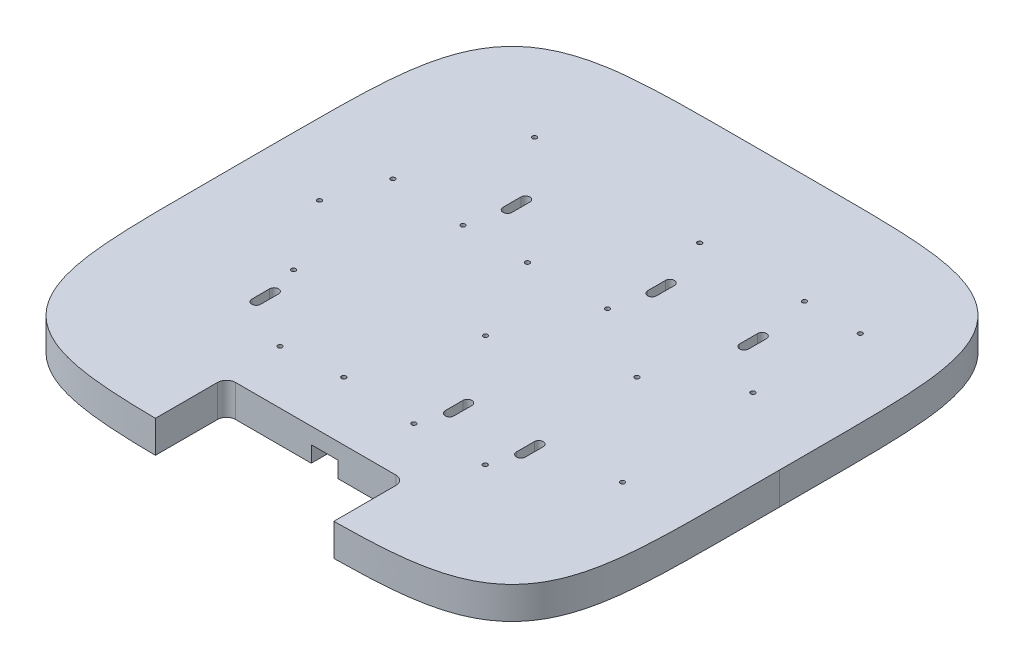
SolidWorks part; units mm, degrees
material "Сосна"
ref_plane "Спереди" through (0, 0, 0) normal (0, 0, 1) x (1, 0, 0)
ref_plane "Сверху" through (0, 0, 0) normal (0, 1, 0) x (1, 0, 0)
ref_plane "Справа" through (0, 0, 0) normal (1, 0, 0) x (0, 0, -1)
sketch "Эскиз основания" plane through (0, 0, 0) normal (0, 1, 0) x (1, 0, 0)
  line L0 (-90, -220) -> (90, -220)
  line L5 (-100, -230) -> (-100, -299.7527)
  line L7 (100, -230) -> (100, -299.7527)
  arc A6 (90, -220) -> (100, -230) centre (90, -230) cw
  arc A7 (-90, -220) -> (-100, -230) centre (-90, -230) ccw
  spline S0 degree 4 poles (300, 0) (299.9998, 8.6944) (299.9997, 21.736) (300.0012, 36.9513) (299.9906, 54.3402) (299.9623, 71.729) (299.8757, 93.4652) (299.6029, 117.242) (298.6794, 143.0506) (297.1967, 163.2872) (295.5862, 177.9573) (293.4888, 191.5009) (291.1341, 202.8581) (288.4089, 213.0451) (285.4103, 222.0487) (282.2757, 229.8814) (278.6208, 237.487) (274.4032, 244.7975) (269.5959, 251.7363) (264.1954, 258.2254) (258.2254, 264.1954) (251.7362, 269.596) (244.7974, 274.4032) (237.487, 278.6209) (229.8814, 282.2757) (222.0487, 285.4104) (213.0451, 288.4089) (202.8581, 291.1341) (191.5009, 293.4888) (177.9573, 295.5862) (163.2872, 297.1967) (143.0506, 298.6794) (117.242, 299.6029) (93.4652, 299.8758) (71.729, 299.9623) (54.3402, 299.9907) (36.9513, 300.0012) (21.736, 299.9997) (8.6944, 299.9998) (0, 300) knots 0 0 0 0 0 0.064453 0.09668 0.112793 0.128906 0.193359 0.257812 0.289062 0.320312 0.34375 0.367188 0.390625 0.40625 0.421875 0.4375 0.453125 0.46875 0.484375 0.5 0.515625 0.53125 0.546875 0.5625 0.578125 0.59375 0.609375 0.632812 0.65625 0.679688 0.710938 0.742188 0.806641 0.871094 0.887207 0.90332 0.935547 1 1 1 1 1 construction
  spline S1 degree 4 poles (300, 0) (299.9998, 8.6944) (299.9997, 21.736) (300.0012, 36.9513) (299.9906, 54.3402) (299.9623, 71.729) (299.8757, 93.4652) (299.6029, 117.242) (298.6794, 143.0506) (297.1967, 163.2872) (295.5862, 177.9573) (293.4888, 191.5009) (291.1341, 202.8581) (288.4089, 213.0451) (285.4103, 222.0487) (282.2757, 229.8814) (278.6208, 237.487) (274.4032, 244.7975) (269.5959, 251.7363) (264.1954, 258.2254) (258.2254, 264.1954) (251.7362, 269.596) (244.7974, 274.4032) (237.487, 278.6209) (229.8814, 282.2757) (222.0487, 285.4104) (213.0451, 288.4089) (202.8581, 291.1341) (191.5009, 293.4888) (177.9573, 295.5862) (163.2872, 297.1967) (143.0506, 298.6794) (117.242, 299.6029) (93.4652, 299.8758) (71.729, 299.9623) (54.3402, 299.9907) (36.9513, 300.0012) (21.736, 299.9997) (8.6944, 299.9998) (0, 300) knots 0 0 0 0 0 0.064453 0.09668 0.112793 0.128906 0.193359 0.257812 0.289062 0.320312 0.34375 0.367188 0.390625 0.40625 0.421875 0.4375 0.453125 0.46875 0.484375 0.5 0.515625 0.53125 0.546875 0.5625 0.578125 0.59375 0.609375 0.632812 0.65625 0.679688 0.710938 0.742188 0.806641 0.871094 0.887207 0.90332 0.935547 1 1 1 1 1
  spline S2 degree 4 poles (300, 0) (299.9998, -8.6944) (299.9997, -21.736) (300.0012, -36.9513) (299.9907, -54.3402) (299.9623, -71.729) (299.8758, -93.4652) (299.6029, -117.242) (298.6794, -143.0506) (297.1967, -163.2872) (295.5862, -177.9573) (293.4888, -191.5009) (291.1341, -202.8581) (288.4089, -213.0451) (285.4104, -222.0487) (282.2757, -229.8814) (278.6209, -237.487) (274.4032, -244.7975) (269.596, -251.7363) (264.1954, -258.2254) (258.2254, -264.1954) (251.7363, -269.596) (244.7975, -274.4032) (237.487, -278.6209) (229.8814, -282.2757) (222.0487, -285.4104) (213.0452, -288.4089) (202.8582, -291.1341) (191.5009, -293.4889) (177.9574, -295.5863) (163.2872, -297.1967) (143.0506, -298.6794) (117.242, -299.6029) (93.4652, -299.8758) (71.729, -299.9624) (54.3403, -299.9907) (36.9514, -300.0013) (21.7361, -299.9997) (8.6945, -299.9999) (0, -300) knots 0 0 0 0 0 0.064453 0.09668 0.112793 0.128906 0.193359 0.257812 0.289062 0.320312 0.34375 0.367188 0.390625 0.40625 0.421875 0.4375 0.453125 0.46875 0.484375 0.5 0.515625 0.53125 0.546875 0.5625 0.578125 0.59375 0.609375 0.632812 0.65625 0.679688 0.710938 0.742188 0.806641 0.871094 0.887207 0.90332 0.935547 1 1 1 1 1 construction
  spline S3 degree 4 poles (300, 0) (299.9998, -8.6944) (299.9997, -21.736) (300.0012, -36.9513) (299.9907, -54.3402) (299.9623, -71.729) (299.8758, -93.4652) (299.6029, -117.242) (298.6794, -143.0506) (297.1967, -163.2872) (295.5862, -177.9573) (293.4888, -191.5009) (291.1341, -202.8581) (288.4089, -213.0451) (285.4104, -222.0487) (282.2757, -229.8814) (278.6209, -237.487) (274.4032, -244.7975) (269.596, -251.7363) (264.1954, -258.2254) (258.2254, -264.1954) (251.7363, -269.596) (244.7975, -274.4032) (237.487, -278.6209) (229.8814, -282.2757) (222.0487, -285.4104) (213.0452, -288.4089) (202.8582, -291.1341) (191.5009, -293.4889) (177.9574, -295.5863) (163.2872, -297.1967) (143.0506, -298.6794) (124.8501, -299.3307) (110.8596, -299.611) (101.083, -299.7393) (100, -299.7527) knots 0 0 0 0 0 0.064453 0.09668 0.112793 0.128906 0.193359 0.257812 0.289062 0.320312 0.34375 0.367188 0.390625 0.40625 0.421875 0.4375 0.453125 0.46875 0.484375 0.5 0.515625 0.53125 0.546875 0.5625 0.578125 0.59375 0.609375 0.632812 0.65625 0.679688 0.710938 0.742188 0.806641 0.81467 0.81467 0.81467 0.81467 0.81467
  spline S4 degree 4 poles (-300, 0) (-299.9998, 8.6944) (-299.9997, 21.736) (-300.0012, 36.9513) (-299.9906, 54.3402) (-299.9623, 71.729) (-299.8757, 93.4652) (-299.6029, 117.242) (-298.6794, 143.0506) (-297.1967, 163.2872) (-295.5862, 177.9573) (-293.4888, 191.5009) (-291.1341, 202.8581) (-288.4089, 213.0451) (-285.4103, 222.0487) (-282.2757, 229.8814) (-278.6208, 237.487) (-274.4032, 244.7975) (-269.5959, 251.7363) (-264.1954, 258.2254) (-258.2254, 264.1954) (-251.7362, 269.596) (-244.7974, 274.4032) (-237.487, 278.6209) (-229.8814, 282.2757) (-222.0487, 285.4104) (-213.0451, 288.4089) (-202.8581, 291.1341) (-191.5009, 293.4888) (-177.9573, 295.5862) (-163.2872, 297.1967) (-143.0506, 298.6794) (-117.242, 299.6029) (-93.4652, 299.8758) (-71.729, 299.9623) (-54.3402, 299.9907) (-36.9513, 300.0012) (-21.736, 299.9997) (-8.6944, 299.9998) (0, 300) knots 0 0 0 0 0 0.064453 0.09668 0.112793 0.128906 0.193359 0.257812 0.289062 0.320312 0.34375 0.367188 0.390625 0.40625 0.421875 0.4375 0.453125 0.46875 0.484375 0.5 0.515625 0.53125 0.546875 0.5625 0.578125 0.59375 0.609375 0.632812 0.65625 0.679688 0.710938 0.742188 0.806641 0.871094 0.887207 0.90332 0.935547 1 1 1 1 1 construction
  spline S5 degree 4 poles (-300, 0) (-299.9998, 8.6944) (-299.9997, 21.736) (-300.0012, 36.9513) (-299.9906, 54.3402) (-299.9623, 71.729) (-299.8757, 93.4652) (-299.6029, 117.242) (-298.6794, 143.0506) (-297.1967, 163.2872) (-295.5862, 177.9573) (-293.4888, 191.5009) (-291.1341, 202.8581) (-288.4089, 213.0451) (-285.4103, 222.0487) (-282.2757, 229.8814) (-278.6208, 237.487) (-274.4032, 244.7975) (-269.5959, 251.7363) (-264.1954, 258.2254) (-258.2254, 264.1954) (-251.7362, 269.596) (-244.7974, 274.4032) (-237.487, 278.6209) (-229.8814, 282.2757) (-222.0487, 285.4104) (-213.0451, 288.4089) (-202.8581, 291.1341) (-191.5009, 293.4888) (-177.9573, 295.5862) (-163.2872, 297.1967) (-143.0506, 298.6794) (-117.242, 299.6029) (-93.4652, 299.8758) (-71.729, 299.9623) (-54.3402, 299.9907) (-36.9513, 300.0012) (-21.736, 299.9997) (-8.6944, 299.9998) (0, 300) knots 0 0 0 0 0 0.064453 0.09668 0.112793 0.128906 0.193359 0.257812 0.289062 0.320312 0.34375 0.367188 0.390625 0.40625 0.421875 0.4375 0.453125 0.46875 0.484375 0.5 0.515625 0.53125 0.546875 0.5625 0.578125 0.59375 0.609375 0.632812 0.65625 0.679688 0.710938 0.742188 0.806641 0.871094 0.887207 0.90332 0.935547 1 1 1 1 1
  spline S6 degree 4 poles (-300, 0) (-299.9998, -8.6944) (-299.9997, -21.736) (-300.0012, -36.9513) (-299.9907, -54.3402) (-299.9623, -71.729) (-299.8758, -93.4652) (-299.6029, -117.242) (-298.6794, -143.0506) (-297.1967, -163.2872) (-295.5862, -177.9573) (-293.4888, -191.5009) (-291.1341, -202.8581) (-288.4089, -213.0451) (-285.4104, -222.0487) (-282.2757, -229.8814) (-278.6209, -237.487) (-274.4032, -244.7975) (-269.596, -251.7363) (-264.1954, -258.2254) (-258.2254, -264.1954) (-251.7363, -269.596) (-244.7975, -274.4032) (-237.487, -278.6209) (-229.8814, -282.2757) (-222.0487, -285.4104) (-213.0452, -288.4089) (-202.8582, -291.1341) (-191.5009, -293.4889) (-177.9574, -295.5863) (-163.2872, -297.1967) (-143.0506, -298.6794) (-117.242, -299.6029) (-93.4652, -299.8758) (-71.729, -299.9624) (-54.3403, -299.9907) (-36.9514, -300.0013) (-21.7361, -299.9997) (-8.6945, -299.9999) (0, -300) knots 0 0 0 0 0 0.064453 0.09668 0.112793 0.128906 0.193359 0.257812 0.289062 0.320312 0.34375 0.367188 0.390625 0.40625 0.421875 0.4375 0.453125 0.46875 0.484375 0.5 0.515625 0.53125 0.546875 0.5625 0.578125 0.59375 0.609375 0.632812 0.65625 0.679688 0.710938 0.742188 0.806641 0.871094 0.887207 0.90332 0.935547 1 1 1 1 1 construction
  spline S7 degree 4 poles (-300, 0) (-299.9998, -8.6944) (-299.9997, -21.736) (-300.0012, -36.9513) (-299.9907, -54.3402) (-299.9623, -71.729) (-299.8758, -93.4652) (-299.6029, -117.242) (-298.6794, -143.0506) (-297.1967, -163.2872) (-295.5862, -177.9573) (-293.4888, -191.5009) (-291.1341, -202.8581) (-288.4089, -213.0451) (-285.4104, -222.0487) (-282.2757, -229.8814) (-278.6209, -237.487) (-274.4032, -244.7975) (-269.596, -251.7363) (-264.1954, -258.2254) (-258.2254, -264.1954) (-251.7363, -269.596) (-244.7975, -274.4032) (-237.487, -278.6209) (-229.8814, -282.2757) (-222.0487, -285.4104) (-213.0452, -288.4089) (-202.8582, -291.1341) (-191.5009, -293.4889) (-177.9574, -295.5863) (-163.2872, -297.1967) (-143.0506, -298.6794) (-124.8501, -299.3307) (-110.8596, -299.611) (-101.083, -299.7393) (-100, -299.7527) knots 0 0 0 0 0 0.064453 0.09668 0.112793 0.128906 0.193359 0.257812 0.289062 0.320312 0.34375 0.367188 0.390625 0.40625 0.421875 0.4375 0.453125 0.46875 0.484375 0.5 0.515625 0.53125 0.546875 0.5625 0.578125 0.59375 0.609375 0.632812 0.65625 0.679688 0.710938 0.742188 0.806641 0.81467 0.81467 0.81467 0.81467 0.81467
  point P15 (0, 0)
  dimension "D10" = 10
  dimension "D6" = 200
  dimension "D8" = 100
  dimension "D2" = 220
  dimension "D3" = 599.9999
extrude "Основание" add sketch "Эскиз основания" against normal blind 36
sketch "Эскиз разметки под крепёж" plane through (0, 0, 0) normal (0, 1, 0) x (1, 0, 0)
  line L0 (-372.0217, 60) -> (388.5777, 60) construction
  line L1 (-372.0217, -160) -> (374.4585, -160) construction
  line L2 (0, -364.7935) -> (0, 383.2318) construction
  circle A0 centre (-115, 60) radius 2.5
  circle A1 centre (47, 60) radius 2.5
  circle A2 centre (210, 60) radius 2.5
  circle A3 centre (-100, -160) radius 2.5
  circle A4 centre (50, -160) radius 2.5
  circle A5 centre (130, -160) radius 2.5
  circle A6 centre (-42.72, 60) radius 2.5
  circle A7 centre (-199.29, 65.75) radius 2.5
  circle A8 centre (-160.19, 185.5) radius 2.5
  circle A9 centre (34.8068, 175.55) radius 2.5
  circle A10 centre (150.2162, 177.55) radius 2.5
  circle A11 centre (212.76, 177.55) radius 2.5
  circle A12 centre (-166.6668, -78.149) radius 2.5
  circle A13 centre (-219.52, 3.7) radius 2.5
  circle A14 centre (-34.29, -154.25) radius 2.5
  circle A15 centre (4.81, -34.5) radius 2.5
  circle A16 centre (223.895, -100) radius 2.5
  circle A17 centre (130, 10) radius 2.5
  dimension "D2" = 5
  dimension "D3" = 5
  dimension "D4" = 5
  dimension "D9" = 5
  dimension "D10" = 5
  dimension "D11" = 5
  dimension "D7" = 5
  dimension "D18" = 5
  dimension "D19" = 5
  dimension "D20" = 5
  dimension "D21" = 5
  dimension "D22" = 5
  dimension "D23" = 5
  dimension "D24" = 5
  dimension "D25" = 5
  dimension "D26" = 5
  dimension "D27" = 5
  dimension "D28" = 5
  dimension "D5" = 60
  dimension "D6" = 220
  dimension "D8" = 130
  dimension "D12" = 50
  dimension "D13" = 100
  dimension "D14" = 210
  dimension "D15" = 47
  dimension "D16" = 115
  dimension "D17" = 89.72
  dimension "D29" = 84.29
  dimension "D30" = 5.75
  dimension "D31" = 125.5
  dimension "D32" = 45.19
  dimension "D33" = 12.1932
  dimension "D34" = 115.55
  dimension "D35" = 2.76
  dimension "D36" = 117.55
  dimension "D37" = 59.7838
  dimension "D38" = 84.29
  dimension "D39" = 5.75
  dimension "D40" = 125.5
  dimension "D41" = 45.19
  dimension "D42" = 81.851
  dimension "D43" = 66.6668
  dimension "D44" = 163.7
  dimension "D45" = 119.52
  dimension "D46" = 170
  dimension "D47" = 93.895
  dimension "D48" = 60
extrude "Разметка под крепёж" cut sketch "Эскиз разметки под крепёж" against normal through all
sketch "Эскиз проерзей для проводов" plane through (0, 0, 0) normal (0, 1, 0) x (1, 0, 0)
  line L0 (-105, 120) -> (-105, 100) construction
  line L1 (-100, 120) -> (-100, 100)
  line L2 (-110, 120) -> (-110, 100)
  line L3 (57, 120) -> (57, 100) construction
  line L4 (62, 120) -> (62, 100)
  line L5 (52, 120) -> (52, 100)
  line L6 (160.2162, 120) -> (160.2162, 100) construction
  line L7 (165.2162, 120) -> (165.2162, 100)
  line L8 (155.2162, 120) -> (155.2162, 100)
  line L9 (-156.6668, -110) -> (-156.6668, -130) construction
  line L10 (-151.6668, -110) -> (-151.6668, -130)
  line L11 (-161.6668, -110) -> (-161.6668, -130)
  line L12 (60, -110) -> (60, -130) construction
  line L13 (65, -110) -> (65, -130)
  line L14 (55, -110) -> (55, -130)
  line L15 (140, -110) -> (140, -130) construction
  line L16 (145, -110) -> (145, -130)
  line L17 (135, -110) -> (135, -130)
  arc A0 (-100, 120) -> (-110, 120) centre (-105, 120) ccw
  arc A1 (-110, 100) -> (-100, 100) centre (-105, 100) ccw
  circle A2 centre (150.2162, 177.55) radius 2.5 construction
  circle A3 centre (-115, 60) radius 2.5 construction
  arc A4 (62, 120) -> (52, 120) centre (57, 120) ccw
  arc A5 (52, 100) -> (62, 100) centre (57, 100) ccw
  circle A6 centre (47, 60) radius 2.5 construction
  arc A7 (165.2162, 120) -> (155.2162, 120) centre (160.2162, 120) ccw
  arc A8 (155.2162, 100) -> (165.2162, 100) centre (160.2162, 100) ccw
  arc A10 (-151.6668, -110) -> (-161.6668, -110) centre (-156.6668, -110) ccw
  arc A11 (-161.6668, -130) -> (-151.6668, -130) centre (-156.6668, -130) ccw
  arc A12 (65, -110) -> (55, -110) centre (60, -110) ccw
  arc A13 (55, -130) -> (65, -130) centre (60, -130) ccw
  arc A14 (145, -110) -> (135, -110) centre (140, -110) ccw
  arc A15 (135, -130) -> (145, -130) centre (140, -130) ccw
  circle A16 centre (-166.6668, -78.149) radius 2.5 construction
  circle A17 centre (50, -160) radius 2.5 construction
  circle A18 centre (130, -160) radius 2.5 construction
  point P2 (-105, 110)
  point P12 (57, 110)
  point P21 (160.2162, 110)
  point P28 (-156.6668, -120)
  point P35 (60, -120)
  point P42 (140, -120)
  dimension "D1" = 5
  dimension "D2" = 100
  dimension "D4" = 5
  dimension "D6" = 5
  dimension "D7" = 5
  dimension "D9" = 5
  dimension "D5" = 5
  dimension "D11" = 5
  dimension "D12" = 5
  dimension "D13" = 5
  dimension "D17" = 5
  dimension "D18" = 5
  dimension "D19" = 5
  dimension "D3" = 20
  dimension "D8" = 20
  dimension "D10" = 20
  dimension "D14" = 20
  dimension "D15" = 20
  dimension "D16" = 20
  dimension "D20" = 110
extrude "Прорезь для проводов" cut sketch "Эскиз проерзей для проводов" against normal through all
ref_plane "Плоскость кабель-канала" through (0, -36, 0) normal (0, 1, 0) x (1, 0, 0)
sketch "Эскиз кабель-канала" plane through (0, -36, 0) normal (0, 1, 0) x (1, 0, 0)
  line L0 (-110, 120) -> (-110, 100) construction
  line L1 (-105, 95) -> (70, 95)
  line L2 (-110, 100) -> (-110, 120)
  line L3 (-105, 125) -> (160.2162, 125)
  line L4 (165.2162, 100) -> (165.2162, 120)
  line L5 (165.2162, 100) -> (165.2162, 120) construction
  line L6 (145, -130) -> (145, -110) construction
  line L7 (-156.6668, -105) -> (70, -105)
  line L8 (-161.6668, -110) -> (-161.6668, -130)
  line L9 (-156.6668, -135) -> (-10, -135)
  line L10 (145, -110) -> (145, -130)
  line L11 (-161.6668, -110) -> (-161.6668, -130) construction
  line L12 (-90, -220) -> (90, -220) construction
  line L14 (75, 90) -> (75, -100)
  line L16 (105, 90) -> (105, -100)
  line L18 (-5, -140) -> (-5, -220)
  line L19 (-5, -220) -> (25, -220)
  line L20 (25, -140) -> (25, -220)
  line L21 (110, 95) -> (160.2162, 95)
  line L22 (110, -105) -> (140, -105)
  line L23 (30, -135) -> (140, -135)
  arc A0 (160.2162, 125) -> (165.2162, 120) centre (160.2162, 120) cw
  arc A1 (160.2162, 95) -> (165.2162, 100) centre (160.2162, 100) ccw
  arc A2 (-105, 95) -> (-110, 100) centre (-105, 100) cw
  arc A3 (-110, 120) -> (-105, 125) centre (-105, 120) cw
  arc A4 (140, -105) -> (145, -110) centre (140, -110) cw
  arc A5 (140, -135) -> (145, -130) centre (140, -130) ccw
  arc A6 (-161.6668, -130) -> (-156.6668, -135) centre (-156.6668, -130) ccw
  arc A7 (-156.6668, -105) -> (-161.6668, -110) centre (-156.6668, -110) ccw
  arc A8 (-10, -135) -> (-5, -140) centre (-10, -140) cw
  arc A9 (30, -135) -> (25, -140) centre (30, -140) ccw
  arc A10 (75, -100) -> (70, -105) centre (70, -100) cw
  arc A11 (110, -105) -> (105, -100) centre (110, -100) cw
  arc A12 (110, 95) -> (105, 90) centre (110, 90) ccw
  arc A13 (70, 95) -> (75, 90) centre (70, 90) cw
  point P15 (-110, 95)
  point P18 (-110, 125)
  point P29 (145, -105)
  point P32 (145, -135)
  point P57 (105, -105)
  dimension "D3" = 5
  dimension "D6" = 5
  dimension "D11" = 5
  dimension "D1" = 30
  dimension "D2" = 95
  dimension "D4" = 30
  dimension "D5" = 105
  dimension "D7" = 30
  dimension "D8" = 30
  dimension "D9" = 5
  dimension "D10" = 75
extrude "Каебель-канал" cut sketch "Эскиз кабель-канала" along normal blind 18
equation "\"box_width\"= 200мм"
equation "\"box_height\"= 80мм"
equation "\"D6@Эскиз основания\"=\"box_width\""
equation "\"drill\"= 5мм"
equation "\"D2@Эскиз разметки под крепёж\" = \"drill\""
equation "\"D3@Эскиз разметки под крепёж\" = \"drill\""
equation "\"D4@Эскиз разметки под крепёж\" = \"drill\""
equation "\"D9@Эскиз разметки под крепёж\" = \"drill\""
equation "\"D10@Эскиз разметки под крепёж\" = \"drill\""
equation "\"D11@Эскиз разметки под крепёж\" = \"drill\""
equation "\"D7@Эскиз разметки под крепёж\"=\"drill\""
equation "\"D18@Эскиз разметки под крепёж\"=\"drill\""
equation "\"D19@Эскиз разметки под крепёж\"=\"drill\""
equation "\"D20@Эскиз разметки под крепёж\"=\"drill\""
equation "\"D21@Эскиз разметки под крепёж\"=\"drill\""
equation "\"D22@Эскиз разметки под крепёж\"=\"drill\""
equation "\"D23@Эскиз разметки под крепёж\"=\"drill\""
equation "\"D24@Эскиз разметки под крепёж\"=\"drill\""
equation "\"D25@Эскиз разметки под крепёж\"=\"drill\""
equation "\"D26@Эскиз разметки под крепёж\"=\"drill\""
equation "\"D27@Эскиз разметки под крепёж\"=\"drill\""
equation "\"D28@Эскиз разметки под крепёж\"=\"drill\""
